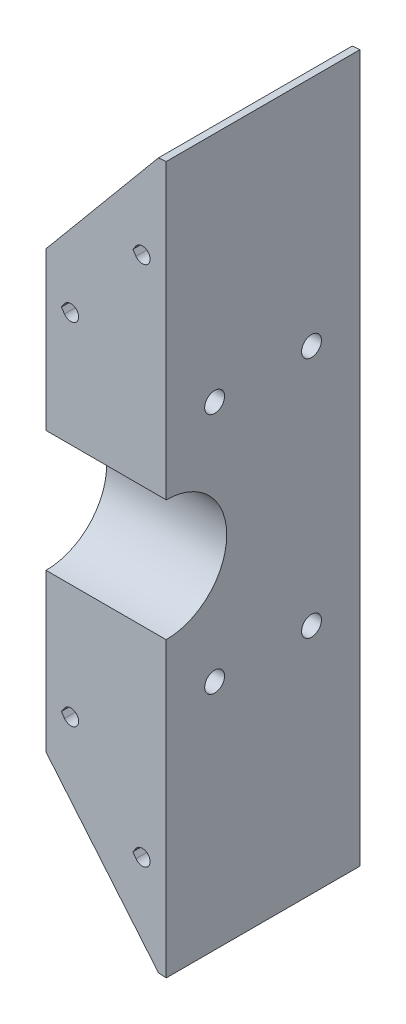
SolidWorks part; units mm, degrees
ref_plane "Front Plane" through (0, 0, 0) normal (1, 0, 0) x (0, 1, 0)
ref_plane "Top Plane" through (0, 0, 0) normal (0, 0, 1) x (0, 1, 0)
ref_plane "Right Plane" through (0, 0, 0) normal (0, 1, 0) x (-1, 0, 0)
sketch "Sketch1" plane through (0, 0, 0) normal (0, 0, 1) x (0, 1, 0)
  line L0 (-75, 0) -> (75, 0) construction
  line L1 (-75, 0) -> (-74.76, 0.2) construction
  line L2 (75, 0) -> (74.76, 0.2) construction
  line L3 (-45, 25) -> (45, 25)
  line L4 (-60, 0) -> (-30, 25) construction
  line L5 (30, 25) -> (60, 0) construction
  line L6 (-53.8542, 5.1215) -> (-53.8542, 7.0747) construction
  line L7 (-36.1458, 19.8785) -> (-36.1458, 21.8318) construction
  line L8 (-54.772, 6.4321) -> (-53.8542, 7.0747)
  line L9 (-52.9365, 6.4321) -> (-53.8542, 7.0747)
  line L10 (-37.0635, 21.1892) -> (-36.1458, 21.8318)
  line L11 (-35.228, 21.1892) -> (-36.1458, 21.8318)
  line L12 (36.1458, 19.8785) -> (36.1458, 21.8318) construction
  line L13 (35.228, 21.1892) -> (36.1458, 21.8318)
  line L14 (37.0635, 21.1892) -> (36.1458, 21.8318)
  line L15 (53.8542, 5.1215) -> (53.8542, 7.0747) construction
  line L16 (52.9365, 6.4321) -> (53.8542, 7.0747)
  line L17 (54.772, 6.4321) -> (53.8542, 7.0747)
  line L18 (-74.76, 0.2) -> (74.76, 0.2)
  line L19 (-74.76, 0.2) -> (-45, 25)
  line L20 (74.76, 0.2) -> (45, 25)
  arc A0 (-54.772, 6.4321) -> (-52.9365, 6.4321) centre (-53.8542, 5.1215) ccw
  arc A1 (-37.0635, 21.1892) -> (-35.228, 21.1892) centre (-36.1458, 19.8785) ccw
  arc A2 (35.228, 21.1892) -> (37.0635, 21.1892) centre (36.1458, 19.8785) ccw
  arc A3 (52.9365, 6.4321) -> (54.772, 6.4321) centre (53.8542, 5.1215) ccw
  point P5 (0, 0)
  point P34 (0, 25)
  dimension "D8" = 3.2
  dimension "D9" = 3.2
  dimension "D15" = 1.6
  dimension "D16" = 1.6
  dimension "D2" = 25
  dimension "D3" = 150
  dimension "D4" = 15
  dimension "D5" = 15
  dimension "D6" = 8
  dimension "D10" = 55
  dimension "D11" = 55
  dimension "D12" = 55
  dimension "D13" = 55
  dimension "D7" = 8
  dimension "D14" = 8
  dimension "D17" = 8
  dimension "D18" = 0.2
  dimension "D19" = 90
extrude "Boss-Extrude1" add sketch "Sketch1" against normal blind 40
sketch "Sketch2" plane through (-25, 0, 0) normal (-1, 0, 0) x (0, -1, 0)
  line L0 (-25, -10) -> (-25, -30) construction
  line L1 (-45, -40) -> (-45, 0) construction
  line L4 (25, -10) -> (25, -30) construction
  line L5 (45, -40) -> (45, 0) construction
  line L6 (-45, -20) -> (45, -20) construction
  line L7 (-45, 0) -> (45, 0) construction
  line L8 (-12.5, 0) -> (12.5, 0)
  circle A0 centre (-25, -10) radius 4
  circle A1 centre (-25, -30) radius 4
  circle A2 centre (-25, -30) radius 2.05
  circle A3 centre (-25, -10) radius 2.05
  circle A4 centre (25, -10) radius 4
  circle A5 centre (25, -10) radius 2.05
  circle A6 centre (25, -30) radius 4
  circle A7 centre (25, -30) radius 2.05
  arc A8 (-12.5, 0) -> (12.5, 0) centre (0, 0) ccw
  point P10 (-25, -20)
  point P11 (25, -20)
  line M4 (45, 0) -> (-45, 0)
  dimension "D6" = 8
  dimension "D5" = 8
  dimension "D7" = 4.1
  dimension "D8" = 4.1
  dimension "D9" = 8
  dimension "D10" = 4.1
  dimension "D11" = 8
  dimension "D12" = 4.1
  dimension "D13" = 12.5
  dimension "D1" = 20
  dimension "D2" = 20
  dimension "D3" = 20
  dimension "D4" = 20
extrude "Cut-Extrude1" cut sketch "Sketch2" against normal through all contours A3 | A2 | A7 | A5 | A8 M4 region at (-25, 0, -5.3052) region at (-25, 25, -30) region at (-25, 25, -10) region at (-25, -25, -10) region at (-25, -25, -30)
extrude "Cut-Extrude2" cut sketch "Sketch2<4>" against normal blind 6
sketch "Sketch2<4>" plane through (-25, 0, 0) normal (-1, 0, 0) x (0, -1, 0) same geometry as "Sketch2"
chamfer "Chamfer1" distance 2.5 angle 45 2 edges at (-0.2, -74.76, -20) (-0.2, 74.76, -20) first distance on face at (-12.6, -59.88, -20) first distance on face at (-12.6, 59.88, -20)
sketch "Sketch3" plane through (0, 0, -40) normal (0, 0, -1) x (1, 0, 0)
  line L1 (-22.6285, 38.8958) -> (-17.1285, 38.8958)
  line L2 (-22.6285, 38.8958) -> (-22.6285, 33.3958)
  line L3 (-22.6285, 33.3958) -> (-17.1285, 33.3958)
  line L4 (-17.1285, 38.8958) -> (-17.1285, 33.3958)
  line L5 (-22.6285, 38.8958) -> (-17.1285, 33.3958) construction
  line L6 (-22.6285, 33.3958) -> (-17.1285, 38.8958) construction
  line L7 (-7.8715, 56.6042) -> (-2.3715, 56.6042)
  line L8 (-7.8715, 56.6042) -> (-7.8715, 51.1042)
  line L9 (-7.8715, 51.1042) -> (-2.3715, 51.1042)
  line L10 (-2.3715, 56.6042) -> (-2.3715, 51.1042)
  line L11 (-7.8715, 56.6042) -> (-2.3715, 51.1042) construction
  line L12 (-7.8715, 51.1042) -> (-2.3715, 56.6042) construction
  line L13 (-22.6285, -33.3958) -> (-17.1285, -33.3958)
  line L14 (-22.6285, -33.3958) -> (-22.6285, -38.8958)
  line L15 (-22.6285, -38.8958) -> (-17.1285, -38.8958)
  line L16 (-17.1285, -33.3958) -> (-17.1285, -38.8958)
  line L17 (-22.6285, -33.3958) -> (-17.1285, -38.8958) construction
  line L18 (-22.6285, -38.8958) -> (-17.1285, -33.3958) construction
  line L19 (-7.8715, -51.1042) -> (-2.3715, -51.1042)
  line L20 (-7.8715, -51.1042) -> (-7.8715, -56.6042)
  line L21 (-7.8715, -56.6042) -> (-2.3715, -56.6042)
  line L22 (-2.3715, -51.1042) -> (-2.3715, -56.6042)
  line L23 (-7.8715, -51.1042) -> (-2.3715, -56.6042) construction
  line L24 (-7.8715, -56.6042) -> (-2.3715, -51.1042) construction
  point P0 (-19.8785, 36.1458)
  point P6 (-5.1215, 53.8542)
  point P12 (-19.8785, -36.1458)
  point P18 (-5.1215, -53.8542)
  dimension "D1" = 5.5
  dimension "D2" = 5.5
  dimension "D3" = 5.5
  dimension "D4" = 5.5
extrude "Cut-Extrude3" cut sketch "Sketch3" against normal blind 5
equation "\"D5@Sketch1\"=\"D4@Sketch1\""
equation "\"D4@Sketch2\"=\"D3@Sketch2\""
equation "\"D2@Sketch3\"=\"D1@Sketch3\""
equation "\"D3@Sketch3\"=\"D1@Sketch3\""
equation "\"D4@Sketch3\"=\"D1@Sketch3\""
